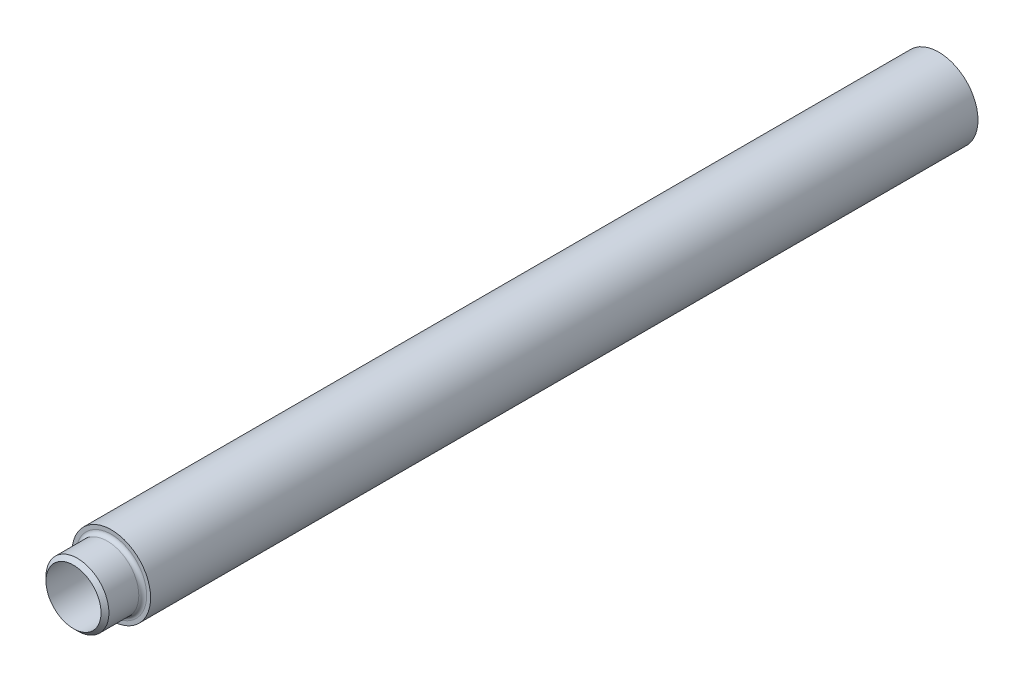
SolidWorks part; units mm, degrees
material "Plain Carbon Steel"
ref_plane "Front Plane" through (0, 0, 0) normal (0, 0, 1) x (1, 0, 0)
ref_plane "Top Plane" through (0, 0, 0) normal (0, 1, 0) x (1, 0, 0)
ref_plane "Right Plane" through (0, 0, 0) normal (1, 0, 0) x (0, 0, -1)
sketch "Sketch1" plane through (0, 0, 0) normal (0, 0, 1) x (1, 0, 0)
  circle A0 centre (0, 0) radius 12.7
  dimension "D1" = 25.4
extrude "Boss-Extrude1" add sketch "Sketch1" along normal blind 279.4
sketch "Sketch2" plane through (0, 0, 0) normal (0, 0, -1) x (-1, 0, 0)
  circle A0 centre (0, 0) radius 8.89
  circle A1 centre (0, 0) radius 12.7 construction
  dimension "D1" = 3.81
extrude "Cut-Extrude1" cut sketch "Sketch2" against normal through all
sketch "Sketch3" plane through (0, 0, 0) normal (0, 0, -1) x (-1, 0, 0)
  circle A0 centre (0, 0) radius 10.033
  circle A1 centre (0, 0) radius 12.7 construction
  dimension "D1" = 2.667
extrude "Cut-Extrude2" cut sketch "Sketch3" against normal blind 12.7
sketch "Sketch4" plane through (0, 0, 279.4) normal (0, 0, 1) x (1, 0, 0)
  circle A0 centre (0, 0) radius 10.16
  circle A1 centre (0, 0) radius 12.7 construction
  circle A2 centre (0, 0) radius 12.7
  dimension "D1" = 2.54
extrude "Cut-Extrude3" cut sketch "Sketch4" against normal blind 12.192
fillet "Fillet1" radius 1.27 1 edges at (10.16, 0, 267.208)
chamfer "Chamfer1" distance 1.27 angle 45 1 edges at (-10.033, 0, 0)
fillet "Fillet2" radius 0.635 1 edges at (-10.033, 0, 12.7)
chamfer "Chamfer2" distance 1.27 angle 45 1 edges at (10.16, 0, 279.4)
